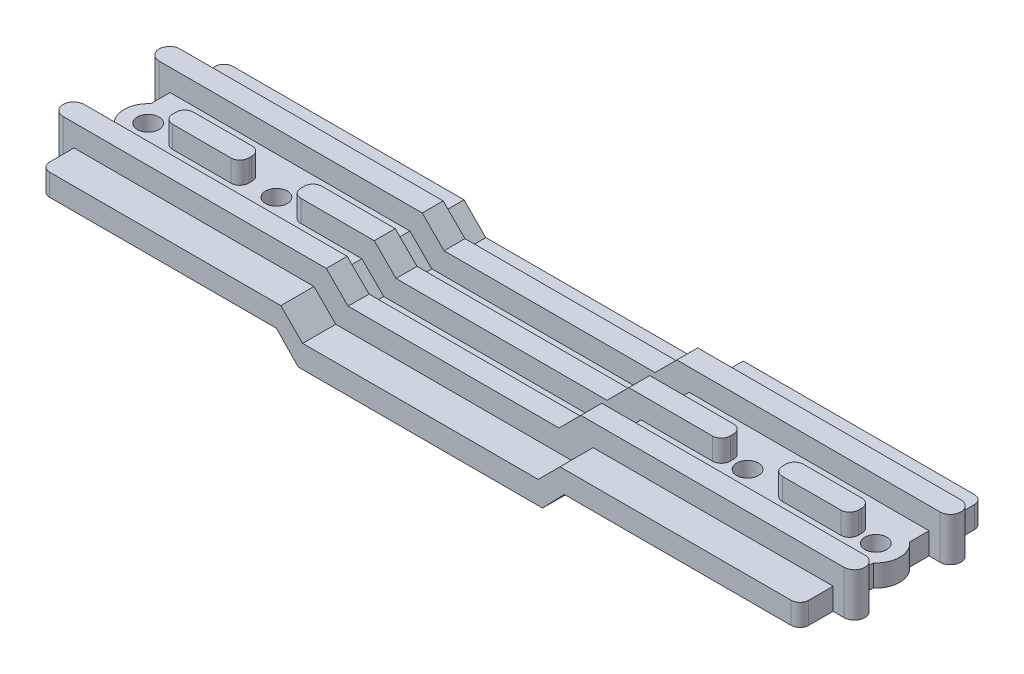
SolidWorks part; units mm, degrees
material "ABS"
ref_plane "Front Plane" through (0, 0, 0) normal (0, 0, 1) x (1, 0, 0)
ref_plane "Top Plane" through (0, 0, 0) normal (0, 1, 0) x (1, 0, 0)
ref_plane "Right Plane" through (0, 0, 0) normal (1, 0, 0) x (0, 0, -1)
sketch "Sketch1" plane through (0, 0, 0) normal (0, 0, 1) x (1, 0, 0)
  line L0 (-43.5, 2.6) -> (-16.5, 2.6)
  line L1 (-14, 0) -> (14, 0)
  line L2 (55, 0) -> (-55, 0) construction
  line L3 (-16.5, 2.6) -> (-14, 0)
  line L4 (-43.5, 2.6) -> (-43.5, 5.1)
  line L5 (-43.5, 5.1) -> (-16, 5.1)
  line L6 (-13.5, 2.6) -> (13.5, 2.6)
  line L7 (0, -55) -> (0, 55) construction
  line L8 (-16, 5.1) -> (-13.5, 2.6)
  line L9 (16, 5.1) -> (13.5, 2.6)
  line L10 (43.5, 5.1) -> (16, 5.1)
  line L11 (43.5, 2.6) -> (43.5, 5.1)
  line L12 (16.5, 2.6) -> (14, 0)
  line L13 (43.5, 2.6) -> (16.5, 2.6)
  point P15 (0, 2.6)
  point P19 (0, 0)
  dimension "D1" = 27
  dimension "D4" = 2.6
  dimension "D6" = 27.5
  dimension "D7" = 13.5
extrude "Boss-Extrude1" add sketch "Sketch1" against normal mid plane 21
sketch "Sketch2" plane through (0, 5.1, 0) normal (0, 1, 0) x (1, 0, 0)
  line L0 (0, 0) -> (27, 0)
  circle A0 centre (27, 0) radius 1.25
  circle A1 centre (41.7, 0) radius 1.25
  dimension "D1" = 27
  dimension "D3" = 2.5
  dimension "D2" = 2.5
extrude "Cut-Extrude1" cut sketch "Sketch2" against normal through all contours A0 | A1 region at (27, 5.1, 1.2146) region at (41.7, 5.1, 0)
mirror "Mirror1" about plane through (0, 0, 0) normal (1, 0, 0) of "Cut-Extrude1"
sketch "Sketch4" plane through (0, 0, 0) normal (0, 0, 1) x (1, 0, 0)
  line L0 (-43.5, 7.6) -> (-14.5878, 7.6)
  line L1 (12.0878, 5.1) -> (-12.0878, 5.1)
  line L2 (0, -4.18) -> (0, 4.18) construction
  line L3 (-14.5878, 7.6) -> (-12.0878, 5.1)
  line L5 (-43.5, 5.1) -> (-43.5, 2.6) construction
  line L6 (-43.5, 7.6) -> (-43.5, 5.1)
  line L7 (-16, 5.1) -> (-43.5, 5.1) construction
  line L8 (-43.5, 5.1) -> (-16, 5.1)
  line L9 (-16, 5.1) -> (-13.5, 2.6)
  line L10 (-13.5, 2.6) -> (13.5, 2.6)
  line L13 (16, 5.1) -> (13.5, 2.6)
  line L14 (43.5, 5.1) -> (16, 5.1)
  line L15 (43.5, 7.6) -> (43.5, 5.1)
  line L17 (14.5878, 7.6) -> (12.0878, 5.1)
  line L18 (43.5, 7.6) -> (14.5878, 7.6)
  dimension "D1" = 0
  dimension "D2" = 2.5
  dimension "D4" = 2.5
  dimension "D5" = 2.5
extrude "Boss-Extrude19" add sketch "Sketch4" along normal mid plane 2.4
mirror "Mirror2" about plane through (0, 0, 0) normal (0, 0, 1) of "Boss-Extrude19"
pattern_linear "LPattern1" count 2 spacing 5.5 along (0, 0, 1) count 2 spacing 5.5 along (0, 0, -1) of "Mirror2" pattern seed only yes
sketch "Sketch5" plane through (0, 7.6, 0) normal (0, 1, 0) x (1, 0, 0)
  circle A0 centre (-41.7, 0) radius 3
  circle A1 centre (-41.7, 0) radius 1.25 construction
  circle A2 centre (-27, 0) radius 3
  circle A3 centre (42.8887, 0) radius 3
  circle A4 centre (28.1887, 0) radius 3
  dimension "D1" = 6
  dimension "D4" = 6
extrude "Cut-Extrude2" cut sketch "Sketch5" against normal blind 2.5
fillet "Fillet1" radius 1 12 edges at (25.4391, 6.35, 1.2) (25.4391, 6.35, -1.2) (40.1391, 6.35, -1.2) (40.1391, 6.35, 1.2) (30.9382, 6.35, -1.2) (30.9382, 6.35, 1.2) (-38.9505, 6.35, -1.2) (-38.9505, 6.35, 1.2) (-29.7495, 6.35, -1.2) (-29.7495, 6.35, 1.2) (-24.2505, 6.35, -1.2) (-24.2505, 6.35, 1.2)
sketch "Sketch6" plane through (0, 7.6, 0) normal (0, 1, 0) x (1, 0, 0)
  line L0 (43.5, -4.3) -> (43.5, -6.7)
  line L1 (43.5, 6.7) -> (43.5, 4.3)
  line L2 (43.5, -6.7) -> (44.75, -6.7)
  line L3 (43.5, -5.5) -> (44.75, -5.5) construction
  line L4 (43.5, -4.3) -> (44.75, -4.3)
  line L5 (43.5, 4.3) -> (44.75, 4.3)
  line L6 (43.5, 6.7) -> (44.75, 6.7)
  line L7 (43.5, 5.5) -> (44.75, 5.5) construction
  line L8 (43.5, -4.3) -> (43.5, 6.7) construction
  line L9 (0, -4.18) -> (0, 4.18) construction
  line L10 (-43.5, -4.3) -> (-43.5, 6.7) construction
  line L11 (-43.5, 5.5) -> (-44.75, 5.5) construction
  line L12 (-43.5, -5.5) -> (-44.75, -5.5) construction
  line L13 (-43.5, 6.7) -> (-44.75, 6.7)
  line L14 (-43.5, 4.3) -> (-44.75, 4.3)
  line L15 (-43.5, -4.3) -> (-44.75, -4.3)
  line L16 (-43.5, -6.7) -> (-44.75, -6.7)
  line L17 (-43.5, 6.7) -> (-43.5, 4.3)
  line L18 (-43.5, -4.3) -> (-43.5, -6.7)
  arc A1 (44.75, -6.7) -> (44.75, -4.3) centre (44.75, -5.5) ccw
  arc A2 (44.75, 4.3) -> (44.75, 6.7) centre (44.75, 5.5) ccw
  arc A3 (-44.75, 4.3) -> (-44.75, 6.7) centre (-44.75, 5.5) cw
  arc A4 (-44.75, -6.7) -> (-44.75, -4.3) centre (-44.75, -5.5) cw
  dimension "D1" = 2
extrude "Boss-Extrude20" add sketch "Sketch6" along direction (0, 1, 0) on the side against the normal blind 5 contours A1 L4 L0 L2 | L1 L5 A2 L6 | A4 L15 L18 L16 | A3 L13 L17 L14
fillet "Fillet2" radius 1 4 edges at (-43.5, 3.85, -10.5) (-43.5, 3.85, 10.5) (43.5, 3.85, -10.5) (43.5, 3.85, 10.5)
sketch "Sketch7" plane through (0, 5.1, 0) normal (0, 1, 0) x (1, 0, 0)
  line L0 (43.5, -2.0791) -> (43.5, 2.0791)
  line L2 (0, -4.18) -> (0, 4.18) construction
  line L3 (-43.5, -2.0791) -> (-43.5, 2.0791)
  arc A0 (43.5, -2.0791) -> (43.5, 2.0791) centre (41.7, 0) ccw
  arc A1 (-43.5, -2.0791) -> (-43.5, 2.0791) centre (-41.7, 0) cw
  dimension "D1" = 5.5
  dimension "D2" = 4.1581
extrude "Boss-Extrude21" add sketch "Sketch7" against normal blind 2.5
equation "\"D7@Sketch1\"=\"D2@Sketch1\"-0.0005"
equation "\"D1@Sketch2\"=.059/2 - 0.0025"
equation "\"D3@Sketch2\"=\"D2@Sketch2\""
equation "\"D4@Sketch5\"=\"D1@Sketch5\""
equation "\"D2@Sketch6\"=\"D3@Sketch6\""
